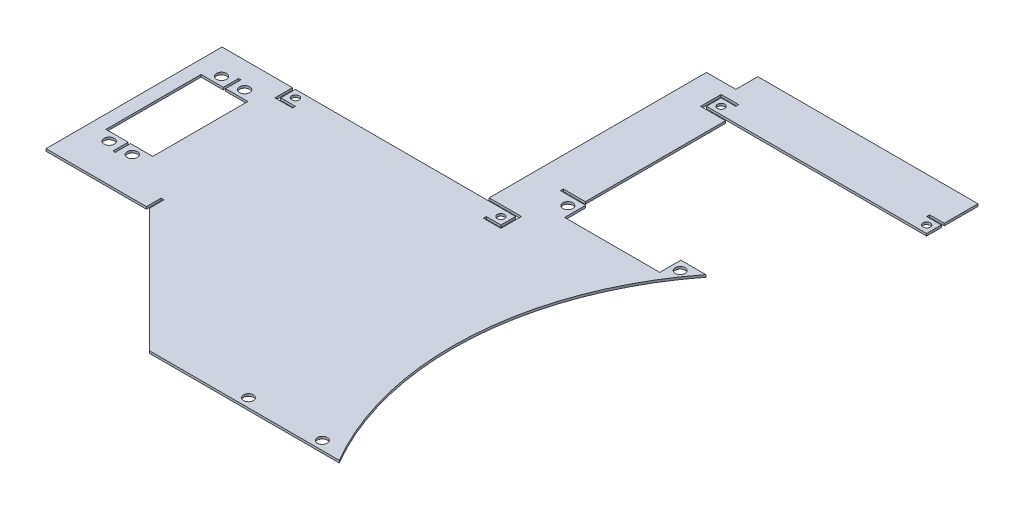
SolidWorks part; units mm, degrees
ref_plane "Front Plane" through (0, 0, 0) normal (0, 0, 1) x (1, 0, 0)
ref_plane "Top Plane" through (0, 0, 0) normal (0, 1, 0) x (1, 0, 0)
ref_plane "Right Plane" through (0, 0, 0) normal (1, 0, 0) x (0, 0, -1)
sketch "Sketch2" plane through (0, 0, 0) normal (0, 1, 0) x (1, 0, 0)
  line L1 (-127, -127) -> (127, -127)
  line L2 (-127, -127) -> (-127, 127)
  line L3 (-127, 127) -> (127, 127)
  line L4 (127, -127) -> (127, 127)
  line L5 (-127, -127) -> (127, 127) construction
  line L6 (-127, 127) -> (127, -127) construction
  point P0 (0, 0)
  dimension "D1" = 254
  dimension "D2" = 254
extrude "Boss-Extrude1" add sketch "Sketch2" along normal blind 1.0008 contours L3 L4 L1 L2
ref_plane "Plane1" through (127, 0, 0) normal (1, 0, 0) x (0, 0, -1)
sketch "Sketch3" plane through (0, 1.0008, 0) normal (0, 1, 0) x (1, 0, 0)
  line L0 (63.5, 41.91) -> (63.5, 3.81) construction
  line L1 (127, 47.252) -> (57.15, 47.252)
  line L2 (127, 47.252) -> (127, 21.852)
  line L3 (127, 21.852) -> (57.15, 21.852)
  line L4 (57.15, 47.252) -> (57.15, 21.852)
  line L7 (64.096, 22.36) -> (70.7, 22.36) construction
  line L8 (64.096, 22.36) -> (70.7, 22.36) construction
  dimension "D1" = 6.35
  dimension "D2" = 0.508
  dimension "D3" = 25.4
extrude "Cut-Extrude1" cut sketch "Sketch3" against normal through all both and the other way through all
sketch "Sketch4" plane through (0, 1.0008, 0) normal (0, 1, 0) x (1, 0, 0)
  line L4 (57.15, 21.852) -> (57.15, 47.252)
  line L5 (127, 127) -> (-127, 127)
  line L6 (127, -127) -> (127, 21.852)
  line L8 (127, 21.852) -> (57.15, 21.852)
  line L11 (-127, -127) -> (127, -127)
  line L12 (127, -127) -> (127, 21.852)
  line L17 (112.9689, -127) -> (127, -127)
  line L18 (127, 21.852) -> (122.64, 21.852)
  line L21 (-127, 127) -> (-127, -127)
  line L22 (57.15, 47.252) -> (127, 47.252)
  line L23 (127, 47.252) -> (127, 127)
  arc A0 (127, 27.1603) -> (114.5024, -129.54) centre (227.33, -59.69) ccw construction
  arc A1 (122.64, 21.852) -> (112.9689, -127) centre (227.33, -59.69) ccw
  dimension "D1" = 0
extrude "Cut-Extrude2" cut sketch "Sketch4" against normal through all both
sketch "Sketch5" plane through (0, 1.0008, 0) normal (0, 1, 0) x (1, 0, 0)
  line L0 (63.5, -129.54) -> (63.5, -61.2891) construction
  circle A0 centre (115.577, 17.86) radius 2.1 construction
  circle A1 centre (66.977, 17.86) radius 2.1 construction
  circle A2 centre (115.577, 17.86) radius 2.1 construction
  circle A3 centre (66.977, 17.86) radius 2.1 construction
  circle A4 centre (69.85, -123.19) radius 2.15
  circle A5 centre (101.8024, -123.19) radius 2.15
  circle A6 centre (66.977, 17.86) radius 2.15
  circle A7 centre (115.577, 17.86) radius 2.15
  dimension "D1" = 6.35
  dimension "D5" = 4.3
  dimension "D2" = 12.7
  dimension "D3" = 6.35
  dimension "D4" = 6.35
extrude "Cut-Extrude3" cut sketch "Sketch5" against normal through all both
sketch "Sketch6" plane through (0, 1.0008, 0) normal (0, 1, 0) x (1, 0, 0)
  line L12 (70.7, 22.36) -> (70.7, 12.733)
  line L13 (70.7, 12.733) -> (111.854, 12.733)
  line L14 (111.854, 12.733) -> (111.854, 22.36)
  line L15 (111.854, 22.36) -> (118.458, 22.36)
  line L16 (118.458, 22.36) -> (118.458, 23.36)
  line L17 (118.458, 23.36) -> (111.854, 23.36)
  line L18 (111.854, 23.36) -> (111.854, 32.987)
  line L19 (111.854, 32.987) -> (70.7, 32.987)
  line L20 (70.7, 32.987) -> (70.7, 23.36)
  line L21 (70.7, 23.36) -> (64.096, 23.36)
  line L22 (64.096, 23.36) -> (64.096, 22.36)
  line L23 (64.096, 22.36) -> (70.7, 22.36)
  line L24 (70.7, 22.36) -> (70.7, 12.733)
  line L25 (70.7, 12.733) -> (111.854, 12.733)
  line L26 (111.854, 12.733) -> (111.854, 22.36)
  line L27 (111.854, 22.36) -> (118.458, 22.36)
  line L28 (118.458, 22.36) -> (118.458, 23.36)
  line L29 (118.458, 23.36) -> (111.854, 23.36)
  line L30 (111.854, 23.36) -> (111.854, 32.987)
  line L31 (111.854, 32.987) -> (70.7, 32.987)
  line L32 (70.7, 32.987) -> (70.7, 23.36)
  line L33 (70.7, 23.36) -> (64.096, 23.36)
  line L34 (64.096, 23.36) -> (64.096, 22.36)
  line L35 (64.096, 22.36) -> (70.7, 22.36)
  circle A1 centre (66.977, 27.86) radius 2.1
  circle A2 centre (66.977, 27.86) radius 2.1
  circle A3 centre (66.977, 17.86) radius 2.1
  circle A4 centre (66.977, 17.86) radius 2.1
  circle A5 centre (115.577, 27.86) radius 2.1
  circle A6 centre (115.577, 27.86) radius 2.1
  circle A7 centre (115.577, 17.86) radius 2.1
  circle A8 centre (115.577, 17.86) radius 2.1
  dimension "D1" = 0
  dimension "D2" = 0
  dimension "D3" = 0
  dimension "D4" = 0
  dimension "D5" = 0
extrude "Cut-Extrude4" cut sketch "Sketch6" against normal through all both
sketch "Sketch7" plane through (0, 1.0008, 0) normal (0, 1, 0) x (1, 0, 0)
  line L1 (-35.5092, 2.4892) -> (59.7408, 2.4892)
  line L2 (-35.5092, 2.4892) -> (-35.5092, 97.7392)
  line L3 (-35.5092, 97.7392) -> (59.7408, 97.7392)
  line L4 (59.7408, 2.4892) -> (59.7408, 97.7392)
  line L5 (-35.5092, 2.4892) -> (59.7408, 97.7392) construction
  line L6 (-35.5092, 97.7392) -> (59.7408, 2.4892) construction
  circle A2 centre (101.6, 22.86) radius 4.7625 construction
  circle A3 centre (101.6, 22.86) radius 4.699 construction
  point P0 (12.1158, 50.1142)
  dimension "D1" = 95.25
  dimension "D3" = 20.3708
  dimension "D2" = 137.1092
extrude "Cut-Extrude5" cut sketch "Sketch7" against normal through all both
sketch "Sketch8" plane through (0, 1.0008, 0) normal (0, 1, 0) x (1, 0, 0)
  line L0 (127, 47.252) -> (127, 127)
  line L2 (127, 127) -> (-127, 127)
  line L3 (-127, 127) -> (-127, -127)
  line L4 (-127, -127) -> (-35.5092, -127)
  line L5 (-127, -127) -> (112.9689, -127) construction
  line L6 (-35.5092, -127) -> (-35.5092, 47.252)
  line L7 (-35.5092, 47.252) -> (127, 47.252)
  line L9 (-35.5092, 97.7392) -> (-35.5092, 2.4892) construction
extrude "Cut-Extrude6" cut sketch "Sketch8" against normal through all both
sketch "Sketch17" plane through (0, 1.0008, 0) normal (0, 1, 0) x (1, 0, 0)
  line L1 (59.7408, 2.4892) -> (47.0408, 2.4892)
  line L2 (59.7408, 2.4892) -> (59.7408, 85.0392)
  line L3 (59.7408, 97.7392) -> (47.0408, 97.7392)
  line L4 (47.0408, 2.4892) -> (47.0408, 97.7392)
  line L5 (-35.5092, 2.4892) -> (59.7408, 2.4892) construction
  line L6 (59.7408, 97.7392) -> (154.9908, 97.7392)
  line L8 (59.7408, 85.0392) -> (154.9908, 85.0392)
  line L9 (154.9908, 97.7392) -> (154.9908, 85.0392)
  dimension "D1" = 12.7
extrude "Boss-Extrude4" add sketch "Sketch17" against normal up to surface (1.0008 mm away) up to face at (62.6286, 0, 13.466)
sketch "Sketch18" plane through (0, 1.0008, 0) normal (0, 1, 0) x (1, 0, 0)
  line L0 (47.0408, 2.4892) -> (59.7408, 2.4892)
extrude "Cut-Extrude-Thin4" cut sketch "Sketch18" against normal through all both and the other way through all thin thin type one direction reverse wall 1.27
sketch "Sketch9" plane through (0, 1.0008, 0) normal (0, 1, 0) x (1, 0, 0)
  line L0 (-35.5092, -60.6947) -> (30.7961, -127)
  line L1 (-35.5092, -127) -> (-35.5092, 2.4892) construction
  line L2 (-35.5092, -127) -> (112.9689, -127) construction
  line L3 (-35.5092, -127) -> (30.7961, -127)
  line L4 (-35.5092, -127) -> (-35.5092, -60.6947)
  circle A0 centre (101.727, 22.86) radius 149.7727 construction
  circle A1 centre (101.727, 22.86) radius 156.1227 construction
  dimension "D1" = 6.35
  dimension "D2" = 45
extrude "Cut-Extrude7" cut sketch "Sketch9" against normal through all both
sketch "Sketch10" plane through (0, 1.0008, 0) normal (0, 1, 0) x (1, 0, 0)
  line L37 (59.7408, 21.852) -> (59.7408, 85.0392) construction
  line L38 (59.7408, 83.7692) -> (69.2658, 83.7692)
  line L39 (59.7408, 83.7692) -> (59.7408, 23.122)
  line L40 (59.7408, 23.122) -> (69.2658, 23.122)
  line L41 (69.2658, 83.7692) -> (69.2658, 23.122)
  line L42 (70.7, 21.852) -> (59.7408, 21.852) construction
  line L43 (59.7408, 85.0392) -> (154.9908, 85.0392) construction
  line L44 (154.9908, 97.7392) -> (47.0408, 97.7392) construction
  line L45 (59.7408, 97.7392) -> (154.9908, 97.7392)
  line L46 (59.7408, 97.7392) -> (59.7408, 107.2642)
  line L47 (59.7408, 107.2642) -> (154.9908, 107.2642)
  line L48 (154.9908, 97.7392) -> (154.9908, 107.2642)
  line M23 (-35.5092, -60.6947) -> (30.7961, -127)
  line M24 (30.7961, -127) -> (112.9689, -127)
  line M33 (-35.5092, 2.4892) -> (-35.5092, -60.6947)
  dimension "D1" = 1.27
  dimension "D2" = 1.27
  dimension "D3" = 9.525
extrude "Boss-Extrude2" add sketch "Sketch10" against normal up to surface (1.0008 mm away) contours M23 | M24 | M33 | L46 L45 L48 L47 | L39 L38 L41 L40 up to face at (69.4486, 0, -10.4541)
sketch "Sketch14" plane through (0, 1.0008, 0) normal (0, 1, 0) x (1, 0, 0)
  line L0 (-61.5112, -12.3358) -> (-41.2572, -53.4898) construction
  line L5 (-61.5112, -12.3358) -> (-51.8842, -12.3358)
  line L6 (-61.5112, -12.3358) -> (-61.5112, -53.4898)
  line L7 (-61.5112, -53.4898) -> (-51.8842, -53.4898)
  line L12 (-41.2572, -12.3358) -> (-41.2572, -53.4898)
  line L17 (-35.5092, -5.1308) -> (-67.2592, -5.1308)
  line L22 (-35.5092, -60.6947) -> (-35.5092, 2.4892) construction
  line L23 (-67.2592, -5.1308) -> (-67.2592, -60.6947)
  line L24 (-67.2592, -60.6947) -> (-35.5092, -60.6947)
  line L25 (-35.5092, -60.6947) -> (-35.5092, -5.1308)
  line L34 (-41.2572, -12.3358) -> (-61.5112, -53.4898) construction
  line L35 (-56.3842, -8.6128) -> (-46.3842, -57.2128) construction
  line L36 (-56.3842, -57.2128) -> (-46.3842, -8.6128) construction
  line L37 (-50.8842, -53.4898) -> (-41.2572, -53.4898)
  line L38 (-51.8842, -53.4898) -> (-51.8842, -60.0938)
  line L39 (-51.8842, -60.0938) -> (-50.8842, -60.0938)
  line L40 (-50.8842, -53.4898) -> (-50.8842, -60.0938)
  line L41 (-51.3842, -32.9128) -> (-15.6253, -32.9128) construction
  line L42 (-51.8842, -5.7318) -> (-50.8842, -5.7318)
  line L43 (-51.8842, -12.3358) -> (-51.8842, -5.7318)
  line L44 (-50.8842, -12.3358) -> (-50.8842, -5.7318)
  line L45 (-50.8842, -12.3358) -> (-41.2572, -12.3358)
  line L47 (-67.2592, -5.1308) -> (-67.2592, 2.4892)
  line L48 (-67.2592, 2.4892) -> (-35.5092, 2.4892)
  line L49 (-35.5092, 2.4892) -> (-35.5092, -5.1308)
  line L51 (-35.5092, 2.4892) -> (59.7408, 2.4892) construction
  line L52 (-67.2592, -60.6947) -> (-67.2592, -73.66)
  line L53 (-67.2592, -73.66) -> (-22.5439, -73.66)
  line L54 (30.7961, -127) -> (-35.5092, -60.6947) construction
  line L57 (-22.5439, -73.66) -> (-35.5092, -60.6947)
  circle A8 centre (-56.3842, -57.2128) radius 2.2
  circle A9 centre (-46.3842, -57.2128) radius 2.2
  circle A10 centre (-56.3842, -8.6128) radius 2.2
  circle A11 centre (-46.3842, -8.6128) radius 2.2
  point P9 (-51.3842, -60.0938)
  point P19 (-51.3842, -32.9128)
  point P20 (-51.3842, -32.9128)
  point P37 (-67.2592, -32.9128)
  point P39 (-51.3842, -60.6947)
  dimension "D3" = 48.6
  dimension "D4" = 4.4
  dimension "D2" = 10
  dimension "D5" = 41.154
  dimension "D6" = 20.254
  dimension "D7" = 1
  dimension "D8" = 6.604
  dimension "D9" = 31.75
  dimension "D10" = 7.62
  dimension "D11" = 53.34
extrude "Boss-Extrude3" add sketch "Sketch14" against normal up to surface (1.0008 mm away) contours L49 L48 L47 L17 | L24 L25 L17 L23 A11 A10 A9 A8 L44 L45 L12 L37 L40 L39 L38 L7 L6 L5 L43 L42 | L24 region at (-36.1492, 1.0008, 32.9128) region at (-51.3842, 1.0008, 1.3208) region at (-47.9597, 1.0008, 67.5437) up to face at (67.7444, 0, -26.3492)
sketch "Sketch15" plane through (0, 1.0008, 0) normal (0, 1, 0) x (1, 0, 0)
  line L0 (-22.5439, -73.66) -> (-22.5439, -67.31)
  dimension "D1" = 6.35
extrude "Cut-Extrude-Thin3" cut sketch "Sketch15" against normal through all both and the other way through all thin thin type one direction reverse wall 1.27
sketch "Sketch19" plane through (0, 1.0008, 0) normal (0, 1, 0) x (1, 0, 0)
  line L0 (154.9908, 85.0392) -> (154.9908, 107.2642) construction
  line L1 (59.7408, 85.0392) -> (154.9908, 85.0392) construction
  line L2 (59.7408, 83.7692) -> (59.7408, 85.0392) construction
  line L3 (-67.2592, 2.4892) -> (59.7408, 2.4892) construction
  line L4 (59.7408, 2.4892) -> (59.7408, 3.7592) construction
  line L5 (62.9158, 88.2142) -> (151.8158, 88.2142) construction
  line L6 (-32.3342, -0.6858) -> (56.5658, -0.6858) construction
  circle A0 centre (56.5658, -0.6858) radius 1.5875
  circle A1 centre (-32.3342, -0.6858) radius 1.5875
  circle A2 centre (151.8158, 88.2142) radius 1.5875
  circle A3 centre (62.9158, 88.2142) radius 1.5875
  dimension "D3" = 3.175
  dimension "D1" = 3.175
  dimension "D2" = 3.175
  dimension "D4" = 3.175
  dimension "D5" = 3.175
  dimension "D6" = 3.175
extrude "Cut-Extrude8" cut sketch "Sketch19" against normal through all both and the other way through all
sketch "Sketch20" plane through (0, 1.0008, 0) normal (0, 1, 0) x (1, 0, 0)
  line L0 (-35.5092, 2.4892) -> (-35.5092, -3.8608)
  line L1 (-67.2592, 2.4892) -> (59.7408, 2.4892) construction
  line L2 (-35.5092, -3.8608) -> (-29.1592, -3.8608)
  line L3 (59.7408, 2.4892) -> (59.7408, -3.8608)
  line L4 (59.7408, -3.8608) -> (53.3908, -3.8608)
  line L5 (59.7408, 85.0392) -> (59.7408, 91.3892)
  line L6 (59.7408, 91.3892) -> (66.0908, 91.3892)
  line L7 (154.9908, 91.3892) -> (154.9908, 85.0392) construction
  line L8 (148.6408, 91.3892) -> (154.9908, 91.3892)
  line L9 (154.9908, 85.0392) -> (154.9908, 107.2642) construction
  line L10 (58.4708, 85.0392) -> (58.4708, 92.6592)
  line L11 (58.4708, 92.6592) -> (66.0908, 92.6592)
  line L12 (148.6408, 92.6592) -> (154.9908, 92.6592)
  line L13 (61.0108, 2.4892) -> (61.0108, -5.1308)
  line L14 (61.0108, -5.1308) -> (53.3908, -5.1308)
  line L15 (-36.7792, 2.4892) -> (-36.7792, -5.1308)
  line L16 (-36.7792, -5.1308) -> (-29.1592, -5.1308)
  line L17 (-36.7792, 2.4892) -> (-35.5092, 2.4892)
  line L18 (-29.1592, -3.8608) -> (-29.1592, -5.1308)
  line L19 (148.6408, 92.6592) -> (148.6408, 91.3892)
  line L20 (154.9908, 91.3892) -> (154.9908, 92.6592)
  line L21 (59.7408, 85.0392) -> (58.4708, 85.0392)
  line L22 (66.0908, 91.3892) -> (66.0908, 92.6592)
  line L23 (59.7408, 2.4892) -> (61.0108, 2.4892)
  line L24 (53.3908, -3.8608) -> (53.3908, -5.1308)
  line L25 (59.7408, 85.0392) -> (59.7408, 83.7692)
  line L26 (59.7408, 83.7692) -> (69.2658, 83.7692) construction
  line L27 (59.7408, 83.7692) -> (58.4708, 83.7692)
  line L28 (58.4708, 83.7692) -> (58.4708, 85.0392)
  line L29 (59.7408, 2.4892) -> (59.7408, 3.7592)
  line L30 (59.7408, 3.7592) -> (61.0108, 3.7592)
  line L31 (61.0108, 3.7592) -> (61.0108, 2.4892)
  dimension "D1" = 6.35
  dimension "D2" = 95.25
  dimension "D3" = 1.27
  dimension "D4" = 1.27
extrude "Cut-Extrude12" cut sketch "Sketch20" against normal through all both contours L28 L27 L25 L21 | L6 L22 L11 L10 L21 L5 | L31 L30 L29 L23 | L4 L24 L14 L13 L23 L3 | L18 L2 L0 L17 L15 L16 | L8 L20 L12 L19 region at (-35.617, 1.0008, 0.6858) region at (60.3758, 1.0008, -2.3814) region at (60.3758, 1.0008, -3.1242) region at (59.1058, 1.0008, -85.147) region at (59.1058, 1.0008, -84.4042)
equation "\"looseTol\"= 0.02in"
equation "\"tightTol\"= 0.005in"
equation "\"normTol\"= 0.01in"
equation "\"D2@Sketch3\"=\"looseTol\""
equation "\"D5@Sketch5\"=4.3mm"
